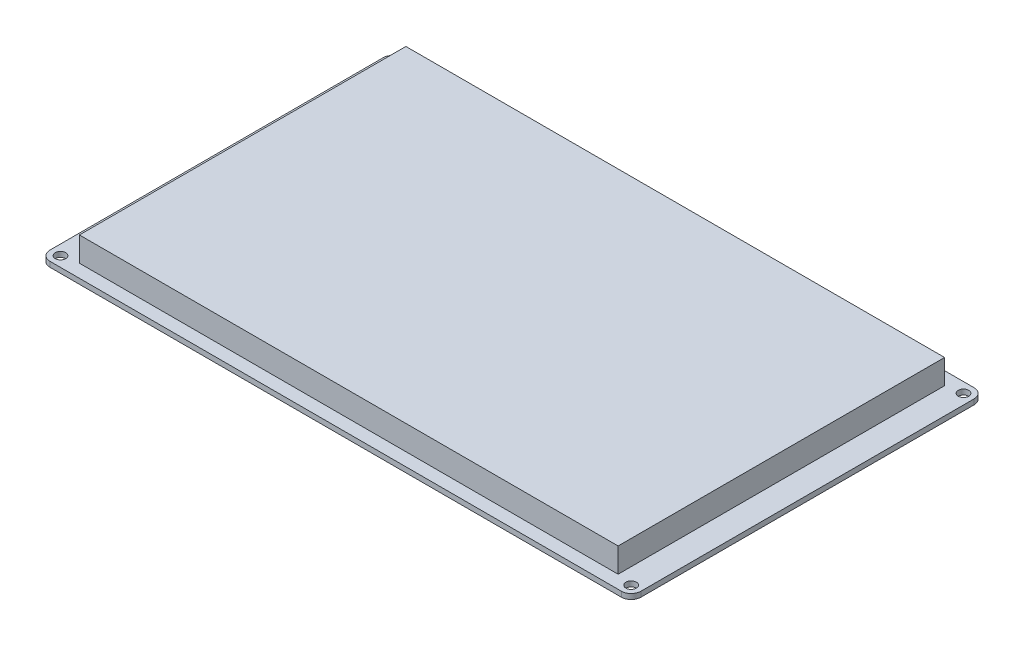
SolidWorks part; units mm, degrees
ref_plane "前视基准面" through (0, 0, 0) normal (0, 0, 1) x (1, 0, 0)
ref_plane "上视基准面" through (0, 0, 0) normal (0, 1, 0) x (1, 0, 0)
ref_plane "右视基准面" through (0, 0, 0) normal (1, 0, 0) x (0, 0, -1)
other "Configuration Table"
sketch "草图1" plane through (0, 0, 0) normal (0, 1, 0) x (1, 0, 0)
  line L0 (0, 0) -> (-90.5, 0) construction
  line L1 (-87.5, -54) -> (87.5, -54)
  line L2 (-90.5, -51) -> (-90.5, 51)
  line L3 (-87.5, 54) -> (87.5, 54)
  line L4 (90.5, -51) -> (90.5, 51)
  line L5 (-90.5, -54) -> (90.5, 54) construction
  line L6 (-90.5, 54) -> (90.5, -54) construction
  line L7 (0, 0) -> (0, 54) construction
  arc A0 (87.5, -54) -> (90.5, -51) centre (87.5, -51) ccw
  arc A1 (-90.5, 51) -> (-87.5, 54) centre (-87.5, 51) cw
  arc A2 (-87.5, -54) -> (-90.5, -51) centre (-87.5, -51) cw
  arc A3 (87.5, 54) -> (90.5, 51) centre (87.5, 51) cw
  circle A4 centre (-87.4, 50.9) radius 1.6
  circle A5 centre (-87.4, -50.9) radius 1.6
  circle A6 centre (87.4, -50.9) radius 1.6
  circle A7 centre (87.4, 50.9) radius 1.6
  point P0 (0, 0)
  dimension "D3" = 3
  dimension "D4" = 3.2
  dimension "D5" = 3.1
  dimension "D6" = 3.1
  dimension "D1" = 181
  dimension "D2" = 108
extrude "凸台-拉伸1" add sketch "草图1" against normal blind 1.6 contours A3 L3 A1 L2 A2 L1 A0 L4 A5 A4 A6 A7 region at (0, 0, 0)
sketch "草图3" plane through (0, 0, 0) normal (0, 1, 0) x (1, 0, 0)
  line L1 (-82.5, -50) -> (82.5, -50)
  line L2 (-82.5, -50) -> (-82.5, 50)
  line L3 (-82.5, 50) -> (82.5, 50)
  line L4 (82.5, -50) -> (82.5, 50)
  line L5 (-82.5, -50) -> (82.5, 50) construction
  line L6 (-82.5, 50) -> (82.5, -50) construction
  point P0 (0, 0)
  dimension "D1" = 165
  dimension "D2" = 100
extrude "凸台-拉伸3" add sketch "草图3" along normal blind 7.5
sketch "草图4" plane through (0, -1.6, 0) normal (0, -1, 0) x (1, 0, 0)
  line L0 (-90.5, 51) -> (-90.5, -51) construction
  line L1 (-90.5, 7.5) -> (-82.5, 7.5)
  line L2 (-90.5, 7.5) -> (-90.5, -7.5)
  line L3 (-90.5, -7.5) -> (-82.5, -7.5)
  line L4 (-82.5, 7.5) -> (-82.5, -7.5)
  line L5 (0, 0) -> (-50000, 0) construction
  line L6 (-90.5, 7.5) -> (-82.5, -7.5) construction
  line L7 (-82.5, 7.5) -> (-90.5, -7.5) construction
  point P9 (-86.5, 0)
  dimension "D1" = 8
  dimension "D2" = 15
extrude "凸台-拉伸4" add sketch "草图4" along normal blind 6
sketch "草图5" plane through (0, -1.6, 0) normal (0, -1, 0) x (1, 0, 0)
  line L0 (-87.5, -54) -> (87.5, -54) construction
  line L1 (69.5, -54) -> (54.5, -54)
  line L2 (69.5, -54) -> (69.5, -39)
  line L3 (69.5, -39) -> (54.5, -39)
  line L4 (54.5, -54) -> (54.5, -39)
  line L5 (90.5, 51) -> (90.5, -51) construction
  dimension "D1" = 21
  dimension "D2" = 15
  dimension "D3" = 15
extrude "凸台-拉伸5" add sketch "草图5" along normal blind 2
